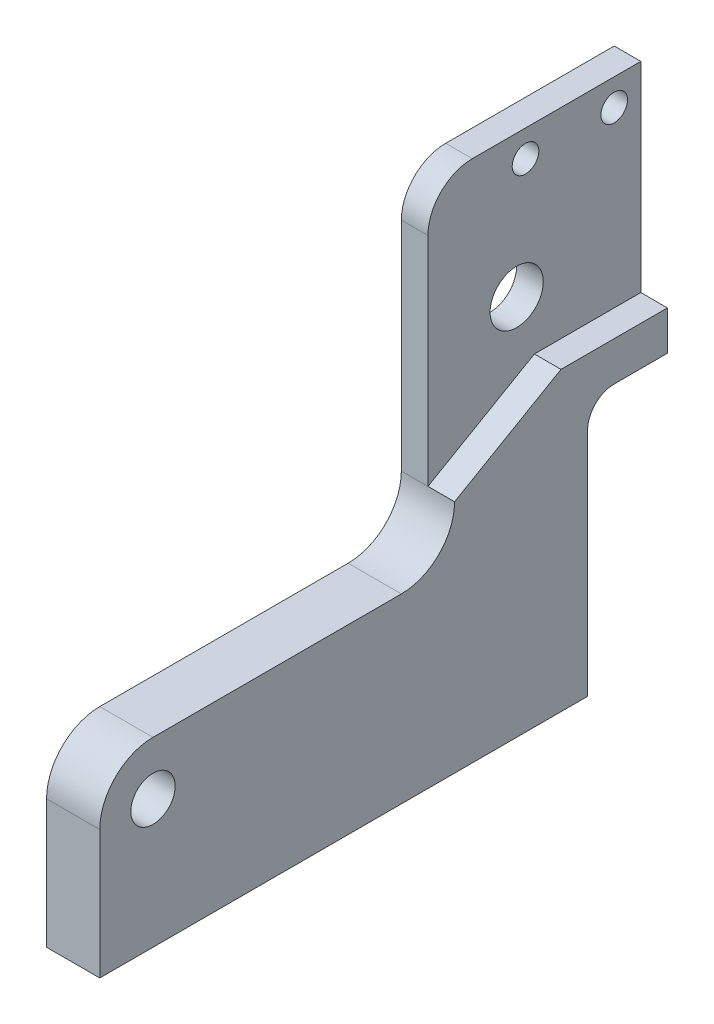
SolidWorks part; units mm, degrees
material "1060 Alloy"
ref_plane "Front Plane" through (0, 0, 0) normal (0, 0, 1) x (1, 0, 0)
ref_plane "Top Plane" through (0, 0, 0) normal (0, 1, 0) x (1, 0, 0)
ref_plane "Right Plane" through (0, 0, 0) normal (1, 0, 0) x (0, 0, -1)
sketch "Sketch1" plane through (0, 0, 0) normal (1, 0, 0) x (0, 0, -1)
  line L1 (0, 0) -> (64, 0)
  line L2 (0, 0) -> (0, 56)
  line L3 (0, 56) -> (64, 56)
  line L4 (64, 0) -> (64, 56)
  circle A0 centre (6, 14.5) radius 2.5
  circle A1 centre (50, 40) radius 3
  dimension "D1" = 6
  dimension "D2" = 5
  dimension "D3" = 14.5
  dimension "D4" = 6
  dimension "D5" = 40
  dimension "D6" = 50
  dimension "D7" = 64
  dimension "D8" = 56
extrude "Boss-Extrude1" add sketch "Sketch1" along normal blind 6
sketch "Sketch3" plane through (6, 0, 0) normal (1, 0, 0) x (0, 0, -1)
  line L1 (0, 56) -> (0, 0) construction
  line L57 (64, 0) -> (55, 0)
  line L58 (64, 0) -> (64, 29)
  line L59 (64, 29) -> (55, 29)
  line L60 (55, 0) -> (55, 29)
  dimension "D1" = 29
  dimension "D2" = 55
extrude "Cut-Extrude2" cut sketch "Sketch3" against normal up to next
fillet "Fillet2" radius 3 1 edges at (3, 29, -55)
hole_wizard "Tap Drill for M3 Tap1" positions "Sketch5" profile "Sketch4" hole size "M3" standard "ISO"
sketch "Sketch5" plane through (0, 0, 0) normal (0, -1, 0) x (-1, 0, 0)
  line L0 (0, 0) -> (0, 55) construction
  line L1 (-6, 0) -> (0, 0) construction
  point P0 (-3, 48)
  point P2 (-3, 12)
  dimension "D1" = 3
  dimension "D2" = 12
  dimension "D3" = 36
sketch "Sketch4" plane through (3, 0, -48) normal (1, 0, 0) x (0, 0, -1)
  line L0 (0, 0) -> (0, 10.7511)
  line L1 (0, 10.7511) -> (1.25, 10)
  line L2 (1.25, 10) -> (1.25, 0)
  line L5 (1.25, 0) -> (0, 0)
  line L10 (0, 10.7511) -> (-1.25, 10) construction
  line L11 (0, -6.35) -> (0, 107.95) construction
  dimension "Hole Dia." = 2.5
  dimension "Hole Depth" = 10
  dimension "Drill Angle" = 118
sketch "Sketch9" plane through (6, 0, 0) normal (1, 0, 0) x (0, 0, -1)
  line L0 (6, 20.5) -> (34, 20.5)
  line L19 (40, 56) -> (40, 26.5)
  line L21 (0, 56) -> (0, 0) construction
  line L22 (40, 56) -> (0, 56)
  line L23 (0, 56) -> (0, 14.5)
  line L24 (0, 56) -> (0, 0) construction
  line L25 (64, 56) -> (0, 56) construction
  arc A0 (40, 26.5) -> (34, 20.5) centre (34, 26.5) cw
  arc A12 (0, 14.5) -> (6, 20.5) centre (6, 14.5) cw
  circle A16 centre (6, 14.5) radius 2.5 construction
  dimension "D1" = 40
extrude "Cut-Extrude3" cut sketch "Sketch9" against normal blind 8
sketch "Sketch13" plane through (6, 0, 0) normal (1, 0, 0) x (0, 0, -1)
  line L0 (64, 29) -> (64, 56) construction
  line L1 (52, 33.4282) -> (64, 33.4282)
  line L2 (64, 56) -> (40, 56) construction
  line L3 (64, 56) -> (40, 56)
  line L4 (64, 33.4282) -> (64, 56)
  line L11 (40, 56) -> (40, 26.5)
  line L12 (40, 26.5) -> (40, 56) construction
  line L15 (40, 26.5) -> (52, 33.4282)
  dimension "D1" = 12
  dimension "D2" = 60
extrude "Cut-Extrude4" cut sketch "Sketch13" against normal blind 3
fillet "Fillet3" radius 5 1 edges at (1.5, 56, -40)
sketch "Sketch14" plane through (3, 0, 0) normal (1, 0, 0) x (0, 0, -1)
  line L0 (64, 33.4282) -> (64, 56) construction
  line L1 (64, 56) -> (45, 56) construction
  circle A0 centre (61, 53) radius 1.5
  circle A1 centre (51, 53) radius 1.5
  dimension "D1" = 3
  dimension "D2" = 10
  dimension "D3" = 3
  dimension "D4" = 3
extrude "Cut-Extrude5" cut sketch "Sketch14" against normal up to next
